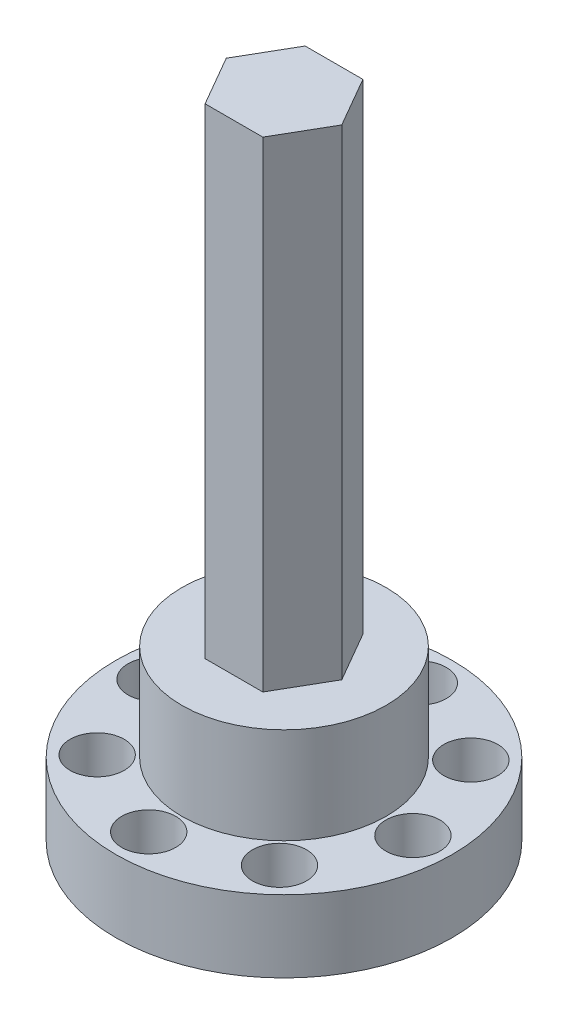
SolidWorks part; units mm, degrees
ref_plane "Front Plane" through (0, 0, 0) normal (0, 0, 1) x (1, 0, 0)
ref_plane "Top Plane" through (0, 0, 0) normal (0, 1, 0) x (1, 0, 0)
ref_plane "Right Plane" through (0, 0, 0) normal (1, 0, 0) x (0, 0, -1)
sketch "Sketch1" plane through (0, 0, 0) normal (0, 1, 0) x (1, 0, 0)
  line L0 (2.7272, -25.8283) -> (2.7272, 18.1717) construction
  line L2 (-4.808, 0) -> (-2.404, -4.1638)
  line L3 (-2.404, -4.1638) -> (2.404, -4.1638)
  line L4 (2.404, -4.1638) -> (4.808, 0)
  line L5 (4.808, 0) -> (2.404, 4.1638)
  line L6 (2.404, 4.1638) -> (-2.404, 4.1638)
  line L7 (-2.404, 4.1638) -> (-4.808, 0)
  circle A0 centre (0, 0) radius 4.1638 construction
extrude "Boss-Extrude1" add sketch "Sketch1" along normal blind 40
ref_plane "Plane2" through (0, 0, 0) normal (0, -1, 0) x (-1, 0, 0)
sketch "Sketch3" plane through (0, 0, 0) normal (0, -1, 0) x (-1, 0, 0)
  circle A0 centre (0, 0) radius 8.5
extrude "Boss-Extrude2" add sketch "Sketch3" along normal blind 8
ref_plane "Plane3" through (0, -8, 0) normal (0, -1, 0) x (-1, 0, 0)
sketch "Sketch4" plane through (0, -8, 0) normal (0, -1, 0) x (-1, 0, 0)
  circle A0 centre (0, 0) radius 14
extrude "Boss-Extrude3" add sketch "Sketch4" along normal blind 6
sketch "Sketch12" plane through (0, 0, 0) normal (1, 0, 0) x (0, 0, -1)
  line L0 (0, 0) -> (0, 50) construction
  circle A0 centre (0, 42) radius 1.5
  dimension "D1" = 8
ref_plane "Plane4" through (0, -14, 0) normal (0, -1, 0) x (-1, 0, 0)
sketch "Sketch13" plane through (0, -14, 0) normal (0, -1, 0) x (-1, 0, 0)
  circle A0 centre (7.5883, 7.9635) radius 1.25
  circle A1 centre (10.9968, 0.2653) radius 1.25
  circle A2 centre (7.9635, -7.5883) radius 1.25
  circle A3 centre (0.2653, -10.9968) radius 1.25
  circle A4 centre (-7.5883, -7.9635) radius 1.25
  circle A5 centre (-10.9968, -0.2653) radius 1.25
  circle A6 centre (-7.9635, 7.5883) radius 1.25
  circle A7 centre (-0.2653, 10.9968) radius 1.25
  point P3 (0, 0)
  point P21 (0, 0)
  dimension "D1" = 11
extrude "Cut-Extrude8" cut sketch "Sketch13" against normal blind 3
sketch "Sketch14" plane through (0, -14, 0) normal (0, -1, 0) x (-1, 0, 0)
  circle A0 centre (0, 0) radius 5.25
extrude "Cut-Extrude9" cut sketch "Sketch14" against normal blind 6
ref_plane "Plane5" through (0, -8, 0) normal (0, 1, 0) x (1, 0, 0)
sketch "Sketch15" plane through (0, -8, 0) normal (0, 1, 0) x (1, 0, 0)
  circle A0 centre (10.9968, -0.2653) radius 2.25
  circle A1 centre (7.5883, -7.9635) radius 2.25
  circle A2 centre (-0.2653, -10.9968) radius 2.25
  circle A3 centre (-7.9635, -7.5883) radius 2.25
  circle A4 centre (-10.9968, 0.2653) radius 2.25
  circle A5 centre (-7.5883, 7.9635) radius 2.25
  circle A6 centre (0.2653, 10.9968) radius 2.25
  circle A7 centre (7.9635, 7.5883) radius 2.25
  point P19 (0, 0)
extrude "Cut-Extrude10" cut sketch "Sketch15" against normal blind 4.5
ref_plane "Plane6" through (0, 40, 0) normal (0, 1, 0) x (1, 0, 0)
sketch "Sketch16" plane through (0, 40, 0) normal (0, 1, 0) x (1, 0, 0)
  line L0 (-0.0071, -6.8572) -> (-0.0071, 6.8541) construction
  line L1 (5.9301, 3.4263) -> (-5.9443, -3.4294) construction
  line L2 (-5.9443, 3.4263) -> (5.9301, -3.4294) construction
ref_plane "Plane7" through (0, -10, 0) normal (0, 1, 0) x (1, 0, 0)
sketch "Sketch20" plane through (0, -10, 0) normal (0, 1, 0) x (1, 0, 0)
  circle A0 centre (-0.0071, -0.0015) radius 12.5
extrude "Boss-Extrude4" [suppressed] add sketch "Sketch20" against normal blind 32
ref_plane "Plane8" [suppressed] through (0, -15, 0) normal (0, 1, 0) x (1, 0, 0)
sketch "Sketch21" plane through (0, 0, 0) normal (0, 0, 1) x (1, 0, 0)
  circle A0 centre (0, -14.0144) radius 1
extrude "Cut-Extrude12" [suppressed] cut sketch "Sketch21" against normal through all and the other way through all contours A0
ref_axis "Axis1" through (0, 7.644, 0) along (0, 1, 0)
ref_plane "Plane9" through (0, 0, 0) normal (0.866, 0, 0.5) x (0, 1, 0)
ref_plane "Plane10" through (0, 0, 0) normal (0.866, 0, -0.5) x (0, 1, 0)
